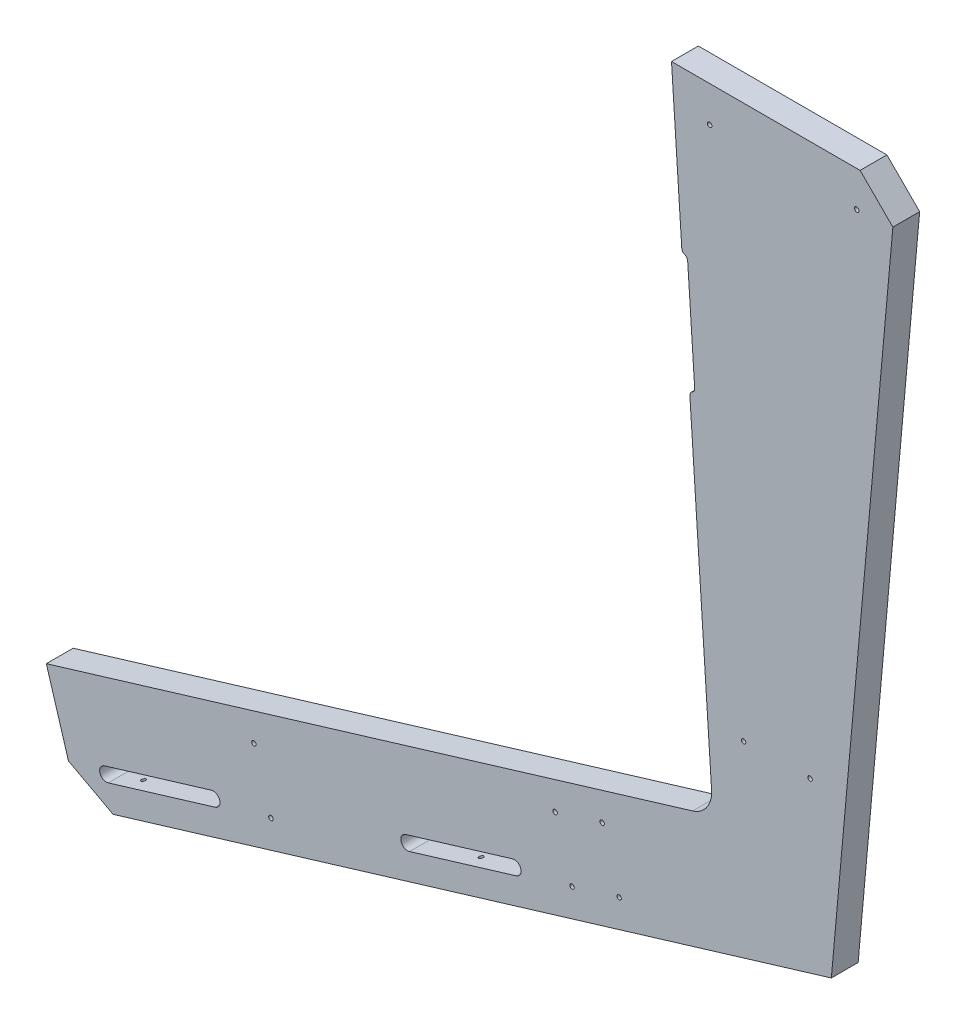
SolidWorks part; units mm, degrees
material "Beech"
ref_plane "Front Plane" through (0, 0, 0) normal (0, 0, 1) x (1, 0, 0)
ref_plane "Top Plane" through (0, 0, 0) normal (0, 1, 0) x (1, 0, 0)
ref_plane "Right Plane" through (0, 0, 0) normal (1, 0, 0) x (0, 0, -1)
sketch "Sketch1" plane through (0, 0, 0) normal (0, 0, 1) x (1, 0, 0)
  line L0 (-3.9531, 12.7) -> (24.5527, -421.626)
  line L1 (-3.9531, 12.7) -> (155.4923, 12.7)
  line L2 (155.4923, 12.7) -> (109.6671, -494.6316)
  line L6 (11.062, -441.1068) -> (-448.2883, -580.1316)
  line L7 (244.2135, 4.6862) -> (-115.2822, 37.1579) construction
  line L8 (-448.2883, -580.1316) -> (-425.1737, -656.504)
  line L11 (-425.1737, -656.504) -> (109.6671, -494.6316)
  arc A1 (24.5527, -421.626) -> (11.062, -441.1068) centre (5.5436, -422.8736) cw
  dimension "D3" = 22
  dimension "D2" = 19.05
  dimension "D1" = 509.397
  dimension "D4" = 79.7937
  dimension "D5" = 558.8
  dimension "D6" = 447.2969
extrude "Boss-Extrude1" add sketch "Sketch1" against normal blind 19.05
ref_plane "CL" through (0, 0, -9.525) normal (0, 0, 1) x (1, 0, 0)
chamfer "Chamfer1" distance 25.4 angle 45 2 edges at (-425.1737, -656.504, -9.525) (155.4923, 12.7, -9.525) first distance on face at (-157.7533, -575.5678, -9.525) first distance on face at (75.7696, 12.7, -9.525)
hole_wizard "3/8 Clearance Slot1" positions "Sketch18" profile "Sketch17" size "3/8" standard "ANSI Inch" slot yes end condition up to next
sketch "Sketch18" plane through (0, 0, 0) normal (0, 0, 1) x (1, 0, 0)
  line L0 (-196.1142, -563.5199) -> (-111.0259, -537.7675) construction
  line L1 (-400.8628, -649.1461) -> (109.6671, -494.6316) construction
  line L3 (11.062, -441.1068) -> (-448.2883, -580.1316) construction
  line L5 (-17.2403, 215.1482) -> (3.9976, -108.4402) construction
  line L7 (-3.9531, 12.7) -> (24.5527, -421.626) construction
  line L8 (-111.0259, -537.7675) -> (29.3862, -495.271) construction
  point P0 (-153.5701, -550.6437)
  point P24 (-367.628, -615.4294)
  dimension "D1" = 88.9
  dimension "D2" = 57.15
  dimension "D3" = 146.7021
  dimension "D4" = 223.647
sketch "Sketch17" plane through (-153.5701, -550.6437, 0) normal (1, 0, 0) x (0, -1, 0)
  line L0 (0, 0) -> (0, 19.05)
  line L1 (0, 19.05) -> (4.7625, 19.05)
  line L2 (4.7625, 19.05) -> (4.7625, 0)
  line L5 (4.7625, 0) -> (0, 0)
  line L11 (0, -6.35) -> (0, 107.95) construction
  dimension "Thru Hole Dia." = 9.525
  dimension "Thru Hole Depth" = 19.05
hole_wizard "Hole6" positions "Sketch19" profile "Sketch20" legacy
sketch "Sketch19" plane through (297.008, -457.8353, 165.475) normal (0.2897, -0.9571, 0) x (0, 0, 1)
  line L0 (-175, 310.0628) -> (-175, 724.4414) construction
  line L3 (-81.55, 824.9675) -> (-81.55, 609.9098) construction
  line L7 (-165.475, 600.3848) -> (0, 600.3848) construction
  line L9 (-175, 376.7378) -> (0, 376.7378) construction
  line L12 (0, 3.9184) -> (0, 227.5654) construction
  point P20 (-81.55, 717.4386)
  point P22 (-81.55, 641.6598)
  point P24 (-81.55, 793.2175)
  point P27 (-175, 705.3914)
  point P29 (-175, 329.1128)
  point P32 (-175, 579.9652)
  point P34 (-175, 454.539)
  point P35 (-175, 517.2521)
  point P50 (-127.375, 600.3848)
  point P52 (-38.1, 600.3848)
  point P61 (-127.375, 376.7378)
  point P63 (-38.1, 376.7378)
  point P74 (38.1, 376.7378)
  point P75 (127.375, 376.7378)
  point P76 (38.1, 600.3848)
  point P77 (127.375, 600.3848)
  point P78 (175, 517.2521)
  point P79 (175, 454.539)
  point P80 (175, 579.9652)
  point P81 (175, 329.1128)
  point P82 (175, 705.3914)
  point P83 (81.55, 793.2175)
  point P84 (81.55, 641.6598)
  point P85 (81.55, 717.4386)
sketch "Sketch20" plane through (-389.6698, -665.6619, 247.025) normal (0, 0, 1) x (0.9571, 0.2897, 0)
  line L0 (0, 0) -> (0, 39.0539)
  line L1 (0, 39.0539) -> (1.5875, 38.1)
  line L2 (1.5875, 38.1) -> (1.5875, 4.0177)
  line L3 (1.5875, 4.0177) -> (5.08, 0)
  line L4 (5.08, 0) -> (0, 0)
  line L5 (0, -14.3089) -> (0, 102.4216) construction
  line L6 (0, 39.0539) -> (-1.5875, 38.1) construction
  line L7 (-1.5875, 4.0177) -> (-5.08, 0) construction
  dimension "Diameter" = 3.175
  dimension "Depth" = 38.1
  dimension "C-Sink Diameter" = 10.16
  dimension "C-Sink Angle" = 82
  dimension "Drill Angle" = 118
hole_wizard "Hole7" positions "Sketch21" profile "Sketch22" legacy
sketch "Sketch21" plane through (155.2867, 10.4243, -19.05) normal (0, 0, -1) x (-0.09, -0.9959, 0)
  line L0 (9.7688, 133.4475) -> (528.1685, 52.1167) construction
  line L5 (0.0093, 25.4) -> (517.3743, 25.4) construction
  line L8 (660.1216, 540.8653) -> (441.5979, 0) construction
  line L11 (698.7793, 525.2466) -> (486.5659, 0) construction
  line L15 (604.5365, 403.2872) -> (643.1942, 387.6685) construction
  line L17 (520.7568, 195.9254) -> (559.4145, 180.3066) construction
  line L19 (507.6737, 163.5435) -> (546.3314, 147.9247) construction
  point P17 (34.8618, 129.5107)
  point P19 (398.7112, 72.427)
  point P22 (25.4093, 25.4)
  point P24 (393.7093, 25.4)
  point P40 (604.5365, 403.2872)
  point P41 (643.1942, 387.6685)
  point P44 (520.7568, 195.9254)
  point P45 (559.4145, 180.3066)
  point P48 (507.6737, 163.5435)
  point P49 (546.3314, 147.9247)
sketch "Sketch22" plane through (-41.186, -520.3847, -19.05) normal (1, 0, 0) x (0, 1, 0)
  line L0 (0, 0) -> (0, 40.64)
  line L1 (0, 40.64) -> (1.5875, 39.6861)
  line L2 (1.5875, 39.6861) -> (1.5875, 4.0177)
  line L3 (1.5875, 4.0177) -> (5.08, 0)
  line L4 (5.08, 0) -> (0, 0)
  line L5 (0, -14.3089) -> (0, 102.4216) construction
  line L6 (0, 40.64) -> (-1.5875, 39.6861) construction
  line L7 (-1.5875, 4.0177) -> (-5.08, 0) construction
  dimension "Diameter" = 3.175
  dimension "Depth" = 40.64
  dimension "C-Sink Diameter" = 10.16
  dimension "C-Sink Angle" = 82
  dimension "Drill Angle" = 118
sketch "Sketch23" plane through (0, 0, -19.05) normal (0, 0, -1) x (-1, 0, 0)
  line L1 (-12.5327, -180.3097) -> (-7.5423, -104.2733)
  line L2 (-9.1121, -186.3666) -> (-2.7757, -186.7825)
  line L3 (-2.7757, -186.7825) -> (2.977, -99.1313)
  line L4 (2.977, -99.1313) -> (-3.3593, -98.7154)
  arc A4 (-9.1121, -186.3666) -> (-10.8224, -183.3381) centre (-12.2803, -186.1586) ccw
  arc A5 (-12.5327, -180.3097) -> (-10.8224, -183.3381) centre (-9.3646, -180.5176) ccw
  arc A6 (-5.4508, -101.4943) -> (-7.5423, -104.2733) centre (-4.3741, -104.4812) ccw
  arc A7 (-5.4508, -101.4943) -> (-3.3593, -98.7154) centre (-6.5275, -98.5075) ccw
  dimension "D1" = 6.35
extrude "Cut-Extrude1" cut sketch "Sketch23" against normal through all
hole_wizard "15/64 (0.23438) Diameter Hole1" positions "Sketch24" profile "Sketch25" hole size "15/64" standard "ANSI Inch"
sketch "Sketch24" plane through (0.6956, 0.0457, 0) normal (-0.9979, -0.0655, 0) x (0, 0, 1)
  point P0 (-9.525, -123.5934)
  point P3 (-9.525, -161.6934)
sketch "Sketch25" plane through (8.7899, -123.2824, -9.525) normal (0, 0, 1) x (0.0655, -0.9979, 0)
  line L0 (0, 0) -> (0, 17.6635)
  line L1 (0, 17.6635) -> (2.9766, 15.875)
  line L2 (2.9766, 15.875) -> (2.9766, 0)
  line L5 (2.9766, 0) -> (0, 0)
  line L10 (0, 17.6635) -> (-2.9766, 15.875) construction
  line L11 (0, -6.35) -> (0, 107.95) construction
  dimension "Hole Dia." = 5.9533
  dimension "Hole Depth" = 15.875
  dimension "Drill Angle" = 118
